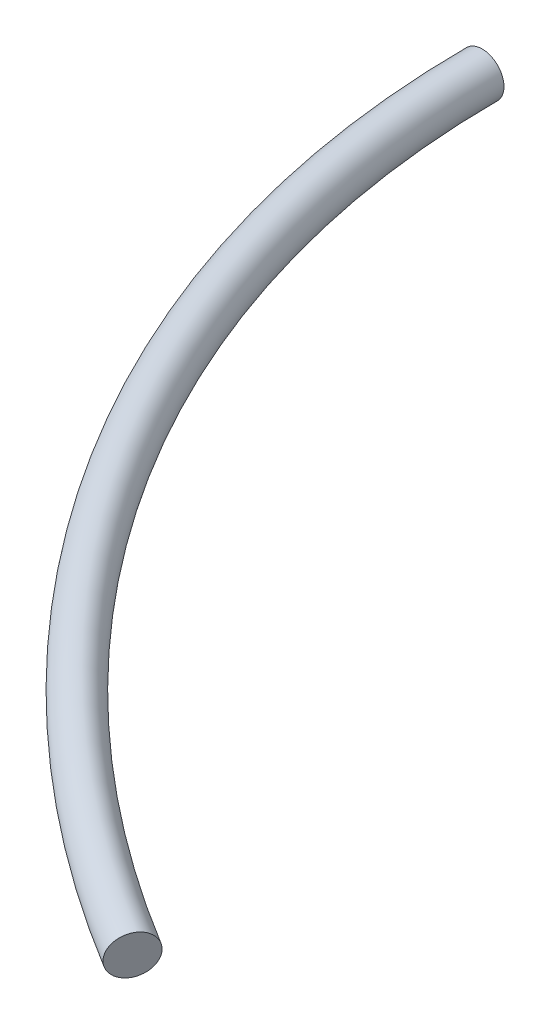
SolidWorks part; units mm, degrees
ref_plane "Front" through (0, 0, 0) normal (0, 0, 1) x (1, 0, 0)
ref_plane "Top" through (0, 0, 0) normal (0, 1, 0) x (1, 0, 0)
ref_plane "Right" through (0, 0, 0) normal (1, 0, 0) x (0, 0, -1)
sketch "Sketch1" plane through (0, 0, 0) normal (0, 0, 1) x (1, 0, 0)
  circle A0 centre (2127.4004, -11945.4645) radius 50.8
ref_plane "Plane1" through (-1859.8113, -11288.5642, 0) normal (0.1626, 0.9867, 0) x (-0.5632, 0.0928, 0.8211)
sketch "Sketch3" plane through (-1859.8113, -11288.5642, 0) normal (0.1626, 0.9867, 0) x (-0.5632, 0.0928, 0.8211)
  line L0 (-2306.6445, 3317.9461) -> (-1351.9224, 5434.3833) construction
  line L1 (-1829.2834, 4376.1647) -> (-1536.6805, 4244.1719) construction
  line L2 (-1351.9224, 5434.3833) -> (-1446.7212, 6249.6276) construction
  line L4 (-2306.6445, 3317.9461) -> (-724.2185, 4418.0527) construction
  arc A0 (-2306.6445, 3317.9461) -> (-1351.9224, 5434.3833) centre (-3596.5419, 5173.3728) ccw
  point P5 (-1337.2598, 5219.0641)
  point P6 (-1465.7553, 4420.9157)
  point P7 (-1866.961, 3719.0711)
  dimension "D1" = 2438.4
  dimension "D2" = 215.9
  dimension "D3" = 812.8
  dimension "D4" = 812.8
sweep "Sweep3" add profiles "Sketch1" path "Sketch3"
ref_axis "Axis1" through (-3964.7352, -6942.5125, 9719.9063) along (0.6153, -0.4399, -0.6541)
